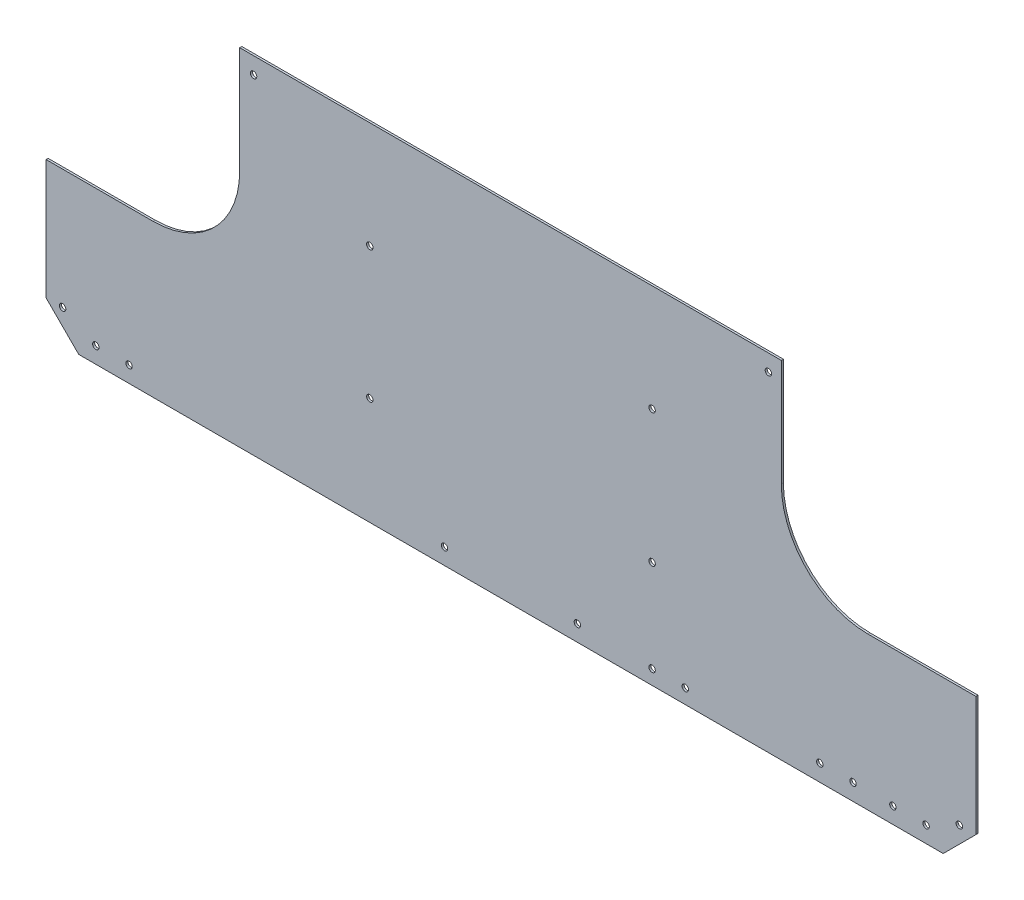
SolidWorks part; units mm, degrees
material "Perspex (TM) GS Acrylic Cast Sheet"
ref_plane "Front Plane" through (0, 0, 0) normal (0, 0, 1) x (1, 0, 0)
ref_plane "Top Plane" through (0, 0, 0) normal (0, 1, 0) x (1, 0, 0)
ref_plane "Right Plane" through (0, 0, 0) normal (1, 0, 0) x (0, 0, -1)
sketch "Sketch1" plane through (0, 0, 0) normal (0, 0, 1) x (1, 0, 0)
  line L1 (-457.2, -304.8) -> (457.2, -304.8)
  line L2 (-457.2, -304.8) -> (-457.2, 304.8)
  line L3 (-457.2, 304.8) -> (457.2, 304.8)
  line L4 (457.2, -304.8) -> (457.2, 304.8)
  line L5 (0, 304.8) -> (0, -304.8) construction
  line L6 (-457.2, 0) -> (457.2, 0) construction
  point P0 (0, 0)
  point P4 (-320.04, 0)
  point P5 (320.04, 0)
  point P6 (0, 213.36)
  point P7 (0, -213.36)
  dimension "Length" = 914.4
  dimension "Width" = 609.6
  dimension "Break" = 137.16
  dimension "D2" = 137.16
  dimension "D1" = 91.44
  dimension "D3" = 91.44
sketch "Sketch2" plane through (0, 0, 0) normal (1, 0, 0) x (0, 0, -1)
  line L0 (-0.7938, -304.8) -> (0.7938, -304.8)
  dimension "Thickness" = 1.5875
sketch "Sketch3" plane through (0, 0, 0) normal (0, 0, 1) x (1, 0, 0)
  line L0 (-457.2, -304.8) -> (-457.2, 304.8) construction
  line L1 (-457.2, -304.8) -> (457.2, -304.8) construction
  line L2 (457.2, -304.8) -> (457.2, 304.8) construction
  line L3 (-457.2, 304.8) -> (457.2, 304.8) construction
  line L4 (-457.2, -304.8) -> (-457.2, 304.8)
  line L5 (-457.2, -304.8) -> (457.2, -304.8)
  line L6 (457.2, -304.8) -> (457.2, 304.8)
  line L7 (-457.2, 304.8) -> (457.2, 304.8)
extrude "Boss-Extrude1" add sketch "Sketch3" along normal mid plane 1.5875
sketch "Sketch4" plane through (0, 0, 0.7937) normal (0, 0, 1) x (1, 0, 0)
  line L17 (-352.1349, -305.1706) -> (-377.5349, -279.7706)
  line L18 (-377.5349, -751.2581) -> (-377.5349, -65.4581) construction
  line L19 (-377.5349, -279.7706) -> (-377.5349, -42.5981)
  line L20 (-374.9949, -40.0581) -> (331.1251, -40.0581)
  line L21 (-352.1349, -305.1706) -> (308.2651, -305.1706)
  line L22 (308.2651, -40.0581) -> (308.2651, -725.8581) construction
  line L23 (308.2651, -305.1706) -> (-352.1349, -305.1706) construction
  line L24 (308.2651, -305.1706) -> (333.6651, -279.7706)
  line L25 (333.6651, -40.0581) -> (333.6651, -725.8581) construction
  line L26 (333.6651, -279.7706) -> (333.6651, -42.5981)
  arc A0 (333.6651, -42.5981) -> (331.1251, -40.0581) centre (331.1251, -42.5981) ccw
  arc A1 (-374.9949, -40.0581) -> (-377.5349, -42.5981) centre (-374.9949, -42.5981) ccw
  point P20 (333.6651, -40.0581)
  point P23 (-377.5349, -40.0581)
  dimension "D1" = 2.54
  dimension "D2" = 2.54
extrude "Cut-Extrude1" cut sketch "Sketch4" against normal blind 2.54 flip side to cut
sketch "Sketch7" plane through (0, 0, 0.7937) normal (0, 0, 1) x (1, 0, 0)
  line L0 (-377.5349, -188.1903) -> (-377.5349, -40.0581)
  line L3 (-377.5349, -40.0581) -> (-229.4027, -40.0581)
  line L10 (-229.4027, -64.7463) -> (-229.4027, -40.0581)
  line L11 (-229.4027, -64.7463) -> (-229.4027, -121.8963)
  line L12 (-352.8467, -188.1903) -> (-295.6967, -188.1903)
  line L13 (-352.8467, -188.1903) -> (-377.5349, -188.1903)
  arc A1 (-229.4027, -121.8963) -> (-295.6967, -188.1903) centre (-295.6967, -121.8963) cw
extrude "Cut-Extrude2" cut sketch "Sketch7" against normal blind 2.54
sketch "Sketch8" plane through (0, 0, 0.7937) normal (0, 0, 1) x (1, 0, 0)
  line L6 (251.1151, -188.1903) -> (336.8401, -188.1903)
  line L7 (336.8401, -188.1903) -> (336.8401, -36.1713)
  line L8 (184.8211, -36.1713) -> (336.8401, -36.1713)
  line L9 (184.8211, -121.8963) -> (184.8211, -36.1713)
  arc A1 (184.8211, -121.8963) -> (251.1151, -188.1903) centre (251.1151, -121.8963) ccw
extrude "Cut-Extrude3" cut sketch "Sketch8" against normal blind 2.54
sketch "Sketch9" plane through (0, 0, 0.7937) normal (0, 0, 1) x (1, 0, 0)
  point P0 (-364.8349, -279.7706)
  point P1 (-339.4349, -292.4706)
  point P3 (-314.0349, -292.4706)
  point P5 (-364.8349, -230.5581)
  point P7 (86.0055, -293.7022)
  point P9 (111.4055, -293.7022)
  point P11 (214.2755, -292.1147)
  point P13 (239.6755, -292.1147)
  point P15 (270.1651, -292.4706)
  point P17 (295.5651, -292.4706)
  point P19 (320.9651, -279.7706)
  point P21 (320.9651, -230.5581)
  point P23 (-218.7849, -52.7581)
  point P25 (174.9151, -52.7581)
hole_wizard "#10 (0.1935) Diameter Hole1" positions "Sketch10" profile "Sketch11" hole size "#10" standard "ANSI Inch" end condition through all
sketch "Sketch10" plane through (0, 0, 0.7937) normal (0, 0, 1) x (1, 0, 0)
  point P0 (-314.0349, -292.4706)
  point P3 (-339.4349, -292.4706)
  point P6 (-364.8349, -279.7706)
  point P9 (86.0055, -293.7022)
  point P12 (111.4055, -293.7022)
  point P15 (214.2755, -292.1147)
  point P18 (239.6755, -292.1147)
  point P21 (295.5651, -292.4706)
  point P24 (270.1651, -292.4706)
  point P27 (320.9651, -279.7706)
  point P31 (174.9151, -52.7581)
  point P34 (-218.7849, -52.7581)
  point P37 (-72.7349, -292.4706)
  point P40 (28.8651, -292.4706)
sketch "Sketch11" plane through (-314.0349, -292.4706, 0.7937) normal (1, 0, 0) x (0, -1, 0)
  line L0 (0, 0) -> (0, 1.5875)
  line L1 (0, 1.5875) -> (2.4574, 1.5875)
  line L2 (2.4574, 1.5875) -> (2.4574, 0)
  line L5 (2.4574, 0) -> (0, 0)
  line L11 (0, -6.35) -> (0, 107.95) construction
  dimension "Thru Hole Dia." = 4.9149
  dimension "Thru Hole Depth" = 1.5875
sketch "Sketch12" plane through (0, 0, 0.7937) normal (0, 0, 1) x (1, 0, 0)
  line L0 (-21.9349, -304.8) -> (-21.9349, -40.0581)
  line L1 (-352.5056, -304.8) -> (308.6357, -304.8) construction
  line L3 (-377.5349, -40.0581) -> (308.2651, -40.0581) construction
  line L8 (-129.8849, -223.2291) -> (86.0151, -223.2291)
  line L10 (-129.8849, -223.2291) -> (-129.8849, -121.6291)
  line L11 (-129.8849, -121.6291) -> (86.0151, -121.6291)
  line L12 (86.0151, -223.2291) -> (86.0151, -121.6291)
  line L13 (-129.8849, -223.2291) -> (86.0151, -121.6291) construction
  line L14 (-129.8849, -121.6291) -> (86.0151, -223.2291) construction
  point P6 (-21.9349, -172.4291)
  point P16 (-21.9349, -304.8)
hole_wizard "#10 (0.1935) Diameter Hole2" positions "Sketch13" profile "Sketch14" hole size "#10" standard "ANSI Inch" end condition through all
sketch "Sketch13" plane through (0, 0, 0.7937) normal (0, 0, 1) x (1, 0, 0)
  line L0 (-129.8849, -223.2291) -> (-129.8849, -121.6291) construction
  point P25 (-129.8849, -121.6291)
  point P28 (-129.8849, -222.541)
  point P32 (86.0151, -223.2291)
  point P35 (86.0151, -121.6291)
sketch "Sketch14" plane through (-129.8849, -121.6291, 0.7937) normal (1, 0, 0) x (0, -1, 0)
  line L0 (0, 0) -> (0, 1.5875)
  line L1 (0, 1.5875) -> (2.4574, 1.5875)
  line L2 (2.4574, 1.5875) -> (2.4574, 0)
  line L5 (2.4574, 0) -> (0, 0)
  line L11 (0, -6.35) -> (0, 107.95) construction
  dimension "Thru Hole Dia." = 4.9149
  dimension "Thru Hole Depth" = 1.5875
equation "\"D1@Boss-Extrude1\"=\"thickness@sketch2\""
equation "\"Break@Sketch1\" = \"Length@Sketch1\" * 0.15"
equation "\"D2@Sketch1\" = \"Break@Sketch1\""
equation "\"D1@Sketch1\"=\"Width@Sketch1\"*0.15"
equation "\"D3@Sketch1\"=\"D1@Sketch1\""
